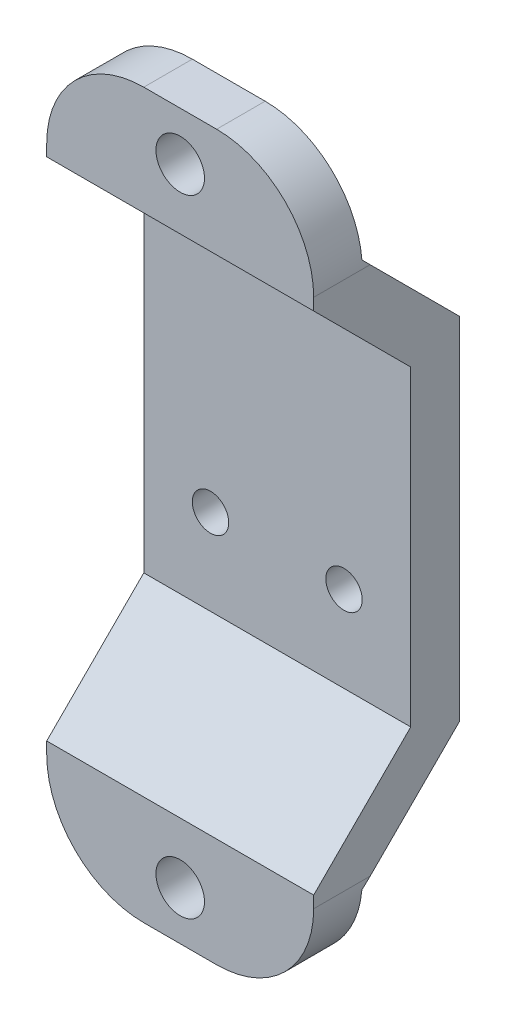
SolidWorks part; units mm, degrees
material "AISI 1035 Steel (SS)"
ref_plane "Front Plane" through (0, 0, 0) normal (0, 0, 1) x (1, 0, 0)
ref_plane "Top Plane" through (0, 0, 0) normal (0, 1, 0) x (1, 0, 0)
ref_plane "Right Plane" through (0, 0, 0) normal (1, 0, 0) x (0, 0, -1)
sketch "Sketch1" plane through (0, 0, 0) normal (1, 0, 0) x (0, 0, -1)
  line L0 (-4.8387, 24.0513) -> (-1.6129, 24.0513)
  line L1 (-1.6129, 24.0513) -> (-1.6129, 18.128)
  line L2 (-4.8387, 24.0513) -> (-4.8387, 16.8123)
  line L3 (1.6129, -10.3607) -> (-4.8387, -16.8123)
  line L4 (4.8387, -11.6764) -> (4.8387, 11.6764)
  line L5 (1.6129, -10.3607) -> (1.6129, 10.3607)
  line L6 (4.8387, 11.6764) -> (-1.6129, 18.128)
  line L7 (1.6129, 10.3607) -> (-4.8387, 16.8123)
  line L9 (4.8387, -11.6764) -> (-1.6129, -18.128)
  line L10 (-4.8387, -24.0513) -> (-4.8387, -16.8123)
  line L11 (-1.6129, -24.0513) -> (-1.6129, -18.128)
  line L12 (-4.8387, -24.0513) -> (-1.6129, -24.0513)
  point P0 (0, 0)
extrude "Boss-Extrude1" add sketch "Sketch1" along normal blind 8.8722 and the other way blind 8.8722
sketch "Sketch2" plane through (0, 0, 4.8387) normal (0, 0, 1) x (1, 0, 0)
  line L0 (-8.8722, 24.0513) -> (-8.8722, 16.8123) construction
  line L1 (-8.8722, 24.0513) -> (8.8722, 24.0513) construction
  circle A0 centre (0, 20.8255) radius 1.6129
  dimension "D1" = 8.8722
  dimension "D2" = 3.2258
  dimension "D3" = 3.2258
extrude "Cut-Extrude1" cut sketch "Sketch2" against normal through all
mirror "Mirror1" about plane through (0, 0, 0) normal (0, 1, 0) of "Cut-Extrude1"
sketch "Sketch3" plane through (0, 0, -1.6129) normal (0, 0, 1) x (1, 0, 0)
  line L0 (-8.8722, 10.3607) -> (-8.8722, -10.3607) construction
  circle A0 centre (-4.4361, -4.6533) radius 1.209
  circle A1 centre (4.4361, -4.6533) radius 1.209
  circle A2 centre (0, -20.8255) radius 1.6129 construction
  circle A3 centre (0, 20.8255) radius 1.6129 construction
  dimension "D1" = 4.4361
  dimension "D2" = 8.8722
  dimension "D3" = 2.4181
  dimension "D4" = 2.4181
  dimension "D5" = 16.1722
extrude "Cut-Extrude2" cut sketch "Sketch3" against normal through all
fillet "Fillet1" radius 6.4516 4 edges at (-8.8722, -24.0513, 3.2258) (8.8722, -24.0513, 3.2258) (8.8722, 24.0513, 3.2258) (-8.8722, 24.0513, 3.2258)
